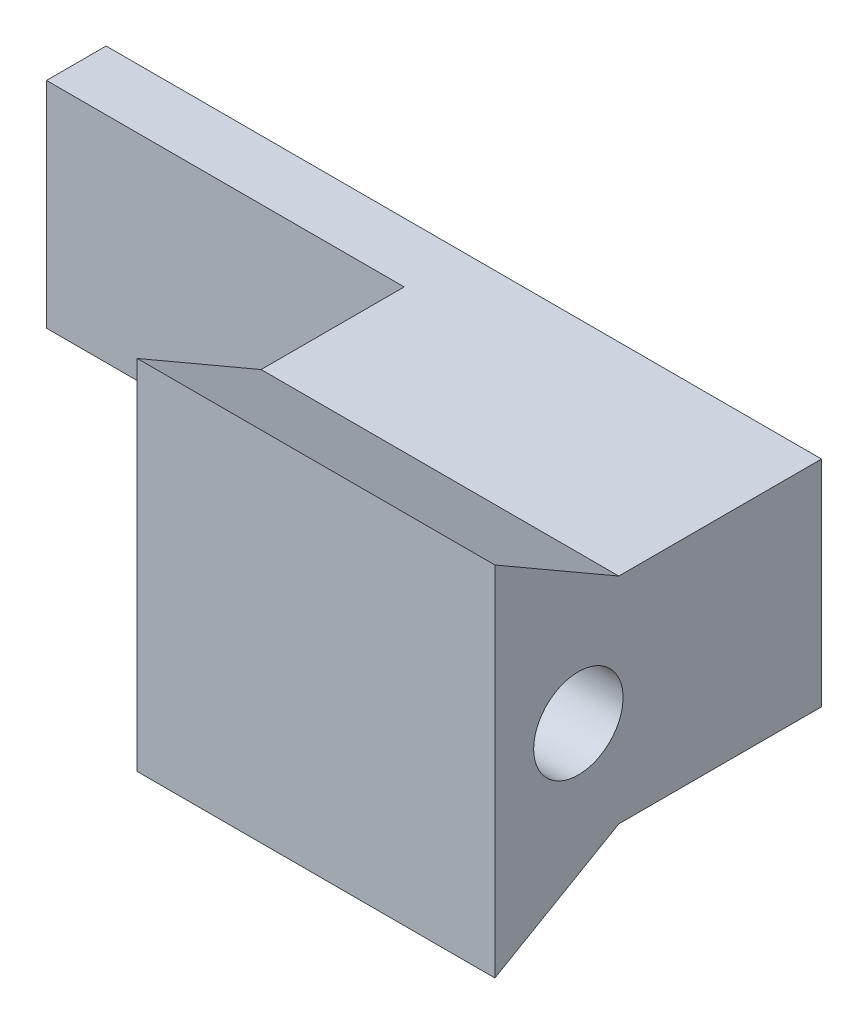
SolidWorks part; units mm, degrees
material "Polyetheretherketone (PEEK)"
ref_plane "Front Plane" through (0, 0, 0) normal (0, 0, 1) x (1, 0, 0)
ref_plane "Top Plane" through (0, 0, 0) normal (0, 1, 0) x (1, 0, 0)
ref_plane "Right Plane" through (0, 0, 0) normal (1, 0, 0) x (0, 0, -1)
sketch "Sketch1" plane through (0, 0, 0) normal (1, 0, 0) x (0, 0, -1)
  line L0 (0, -1.5) -> (0, 1.5)
  line L1 (0, 1.5) -> (1.0392, 0.9)
  line L2 (1.0392, -0.9) -> (2.2392, -0.9)
  line L4 (2.7392, 0.9) -> (2.7392, -0.9)
  line L5 (2.7392, -0.9) -> (2.2392, -0.9)
  line L7 (1.0392, -0.9) -> (0, -1.5)
  line L8 (1.0392, 0.9) -> (2.2392, 0.9)
  line L11 (2.7392, -0.9) -> (2.2392, -0.9)
  line L12 (2.7392, -0.9) -> (2.7392, 0.9)
  line L13 (2.7392, 0.9) -> (2.2392, 0.9)
  line L14 (2.2392, -0.9) -> (2.2392, 0.9)
  line L15 (2.7392, -0.9) -> (2.2392, 0.9) construction
  line L16 (2.7392, 0.9) -> (2.2392, -0.9) construction
  point P3 (0.7, 0)
  point P4 (0, 0)
  point P12 (2.7392, 0)
  point P13 (2.4892, 0)
  dimension "D1" = 3
  dimension "D2" = 60
  dimension "D3" = 60
  dimension "D4" = 1.8
  dimension "D6" = 1.2
  dimension "D7" = 1.8
  dimension "D8" = 0
  dimension "D9" = 0.7
  dimension "D10" = 0
  dimension "D11" = 0
  dimension "D13" = 1.8
  dimension "D5" = 0.5
  dimension "D12" = 1.2
extrude "Boss-Extrude1" add sketch "Sketch1" along normal blind 3 contours L8 L1 L0 L7 L2 | L5 L4 | L4 L11 L5 | L13 L4 region at (0, 0, -1.016) region at (0, 0, -2.4892)
hole_wizard "M1x0.25 Tapped Hole1" positions "Sketch2" profile "Sketch3" tap size "M1x0.25" standard "JIS" end condition through all
sketch "Sketch2" plane through (0, 0, 0) normal (-1, 0, 0) x (0, 0, 1)
  line L0 (0, -1.5) -> (0, 1.5) construction
  point P0 (-0.7, 0)
  dimension "D1" = 0.7
  dimension "D2" = 0
sketch "Sketch3" plane through (0, 0, -0.7) normal (0, 1, 0) x (0, 0, 1)
  line L0 (0, 0) -> (0, 3)
  line L1 (0, 3) -> (0.375, 3)
  line L2 (0.375, 3) -> (0.375, 0)
  line L5 (0.375, 0) -> (0, 0)
  line L11 (0, -6.35) -> (0, 107.95) construction
  dimension "Thru Tap Drill Dia." = 0.75
  dimension "Thru Tap Drill Depth" = 3
cosmetic thread "Hole Thread1" parameters "D2"=1
extrude "Boss-Extrude2" add sketch "Sketch1<5>" against normal blind 3 contours L14 L5 L4 L13 region at (0, 0, -2.4892)
sketch "Sketch1<5>" plane through (0, 0, 0) normal (1, 0, 0) x (0, 0, -1) same geometry as "Sketch1"
equation "\"D12@Sketch1\"=\"D6@Sketch1\""
